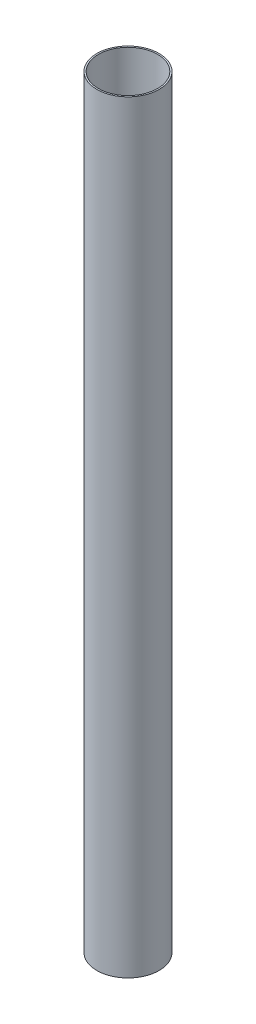
SolidWorks part; units mm, degrees
material "6063-T6"
ref_plane "Front Plane" through (0, 0, 0) normal (0, 0, 1) x (1, 0, 0)
ref_plane "Top Plane" through (0, 0, 0) normal (0, 1, 0) x (1, 0, 0)
ref_plane "Right Plane" through (0, 0, 0) normal (1, 0, 0) x (0, 0, -1)
sketch "Sketch1" plane through (0, 0, 0) normal (0, 1, 0) x (1, 0, 0)
  circle A0 centre (0, 0) radius 24.1554
  circle A1 centre (0, 0) radius 25.4
  dimension "D1" = 50.8
  dimension "D2" = 1.2446
extrude "body" add sketch "Sketch1" along normal blind 622.3
